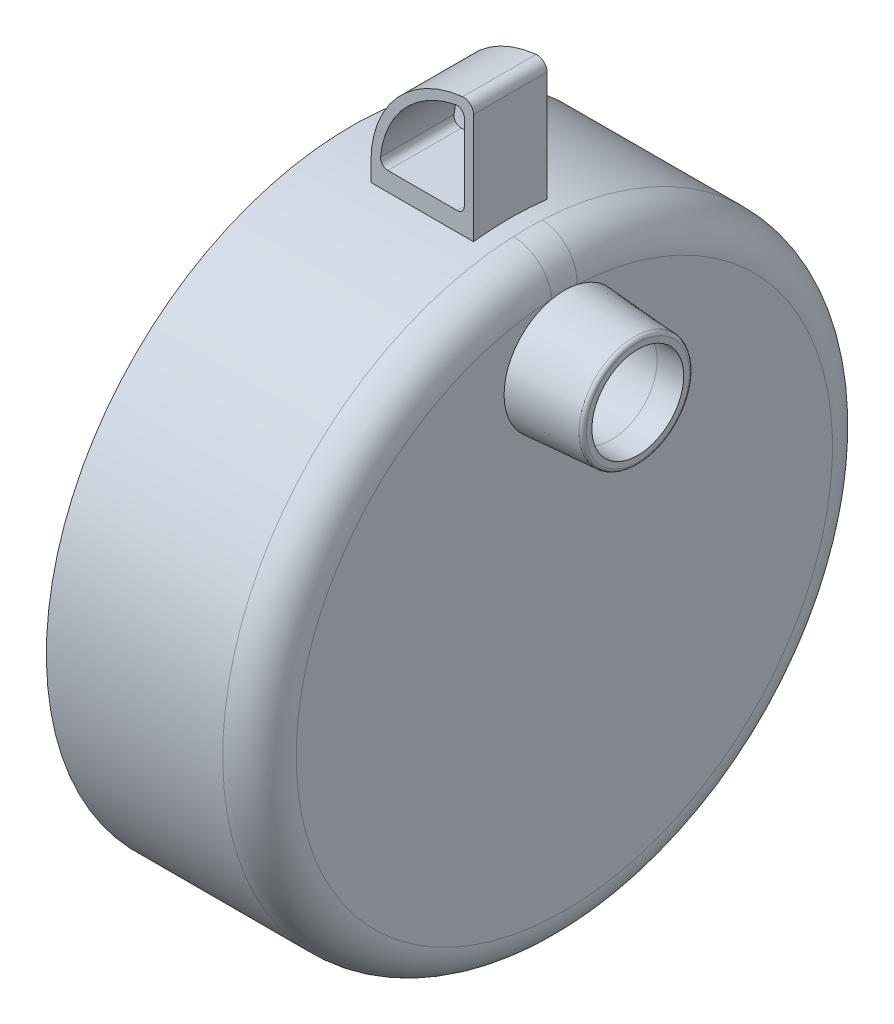
SolidWorks part; units mm, degrees
ref_plane "Front Plane" through (0, 0, 0) normal (0, 0, 1) x (1, 0, 0)
ref_plane "Top Plane" through (0, 0, 0) normal (0, 1, 0) x (1, 0, 0)
ref_plane "Right Plane" through (0, 0, 0) normal (1, 0, 0) x (0, 0, -1)
sketch "Sketch2" plane through (0, 0, 0) normal (0, 0, 1) x (1, 0, 0)
  line L0 (0, 0) -> (-8.6314, 0) construction
  line L1 (-6.6626, 0) -> (-6.6626, 8.3)
  line L2 (-6.6626, 8.3) -> (-0.6626, 8.3)
  line L3 (-0.6626, 8.3) -> (-0.6626, 0)
  line L4 (-0.6626, 0) -> (-6.6626, 0)
  dimension "D1" = 6
  dimension "D2" = 8.3
revolve "Revolve1" add sketch "Sketch2" angle 360 about L0
sketch "Sketch3" plane through (0, 0, 0) normal (0, 0, 1) x (1, 0, 0)
  line L1 (-0.6626, -8.3) -> (-0.6626, 8.3) construction
  line L2 (-0.6626, 7.3283) -> (1.3374, 7.1885)
  line L3 (1.3374, 7.1885) -> (1.3374, 5.6885)
  line L4 (1.3374, 5.6885) -> (-0.6626, 5.6885)
  line L5 (-0.6626, 5.6885) -> (-0.6626, 7.3283)
  line L6 (-0.6626, 5.6885) -> (6.4748, 5.6885) construction
  line L7 (1.3374, 7.1885) -> (-0.6626, 7.1885) construction
  dimension "D1" = 1.5
  dimension "D2" = 4
  dimension "D3" = 2
revolve "Revolve2" add sketch "Sketch3" angle 360 about L6 region at (0.3225, 6.4739, 0)
shell "Shell1" thickness 0.3 removed face at (-6.6626, 8.3, 0)
sketch "Sketch5" plane through (1.3374, 0, 0) normal (1, 0, 0) x (0, 0, -1)
  circle A0 centre (0, 5.6885) radius 1.25
  dimension "D1" = 2.5
extrude "Cut-Extrude1" cut sketch "Sketch5" against normal blind 10
fillet "Fillet1" radius 1 1 edges at (-0.6626, 8.3, 0)
fillet "Fillet2" radius 0.1 1 edges at (1.3374, 4.1885, 0)
chamfer "Chamfer1" distance 0.5 angle 45 1 edges at (-6.6626, -8, 0)
sketch "Sketch6" plane through (0, 0, 0) normal (0, 0, 1) x (1, 0, 0)
  line L0 (-4.9279, 8.3) -> (-4.9279, 8.7303)
  line L1 (-1.6622, 8.3) -> (-6.4626, 8.3) construction
  line L2 (-2.134, 11.2407) -> (-2.134, 8.1159)
  line L3 (-2.134, 8.1159) -> (-4.9279, 8.1159)
  line L4 (-4.9279, 8.1159) -> (-4.9279, 7.7144)
  line L5 (-4.4673, 8.7529) -> (-2.584, 8.7529)
  line L6 (-2.384, 8.9529) -> (-2.384, 11.0306)
  line L7 (-4.9279, 8.3) -> (-4.9279, 7.7144)
  arc A0 (-4.9279, 8.7303) -> (-2.4319, 11.5083) centre (-2.134, 8.7303) cw
  arc A1 (-2.4319, 11.5083) -> (-2.134, 11.2407) centre (-2.4032, 11.2407) cw
  arc A2 (-4.6664, 8.9718) -> (-2.6224, 11.2269) centre (-2.134, 8.7303) cw
  arc A3 (-2.6224, 11.2269) -> (-2.384, 11.0306) centre (-2.584, 11.0306) cw
  arc A4 (-2.584, 8.7529) -> (-2.384, 8.9529) centre (-2.584, 8.9529) ccw
  arc A5 (-4.6664, 8.9718) -> (-4.4673, 8.7529) centre (-4.4673, 8.9529) ccw
  dimension "D1" = 0.25
  dimension "D3" = 0.2
  dimension "D2" = 0.25
extrude "Boss-Extrude1" add sketch "Sketch6" along normal mid plane 2 contours A1 A0 L0 L4 L3 L2 A5 A2 A3 L6 A4 L5 region at (-4.8839, 8.5152, 0)
